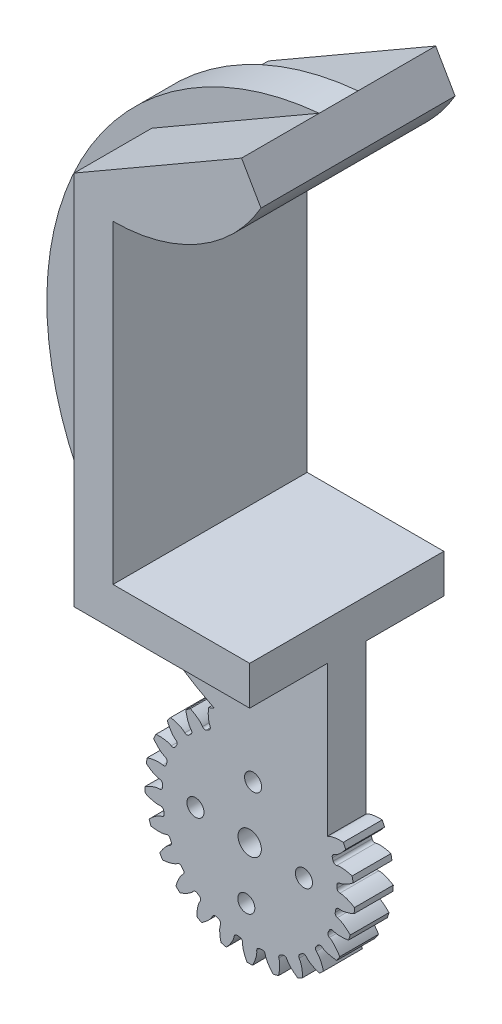
SolidWorks part; units mm, degrees
ref_plane "前视基准面" through (0, 0, 0) normal (0, 0, 1) x (1, 0, 0)
ref_plane "上视基准面" through (0, 0, 0) normal (0, 1, 0) x (1, 0, 0)
ref_plane "右视基准面" through (0, 0, 0) normal (1, 0, 0) x (0, 0, -1)
ref_axis "Axis1" through (0, 0, -88.99) along (0, 0, 1)
sketch "草图1" plane through (0, 0, 0) normal (0, 0, 1) x (1, 0, 0)
  circle A0 centre (0, 0) radius 13.5
extrude "LaShenA" add sketch "草图1" along normal blind 5
sketch "SketchA" plane through (0, 0, 5) normal (0, 0, 1) x (1, 0, 0)
  line L0 (0, 0) -> (0, 13.5) construction
  arc A0 (0.1684, 11.2487) -> (-0.1684, 11.2487) centre (0, 0) ccw
  arc A1 (1.8042, 14.0286) -> (-1.8042, 14.0286) centre (0, 0) ccw
  arc A2 (-0.1684, 11.2487) -> (-0.5533, 11.6043) centre (-0.1741, 11.6287) cw
  arc A3 (0.5533, 11.6043) -> (0.1684, 11.2487) centre (0.1741, 11.6287) cw
  circle A4 centre (0, 0) radius 11.7462 construction
  circle A5 centre (0, 0) radius 13.5 construction
  circle A6 centre (0, 0) radius 11.25 construction
  circle A7 centre (0, 0) radius 12.5 construction
  spline S0 degree 3 poles (0.5533, 11.6043) (0.5561, 11.6473) (0.5611, 11.7224) (0.5725, 11.8116) (0.5848, 11.8743) (0.5957, 11.9239) (0.6097, 11.9808) (0.6273, 12.0449) (0.6489, 12.116) (0.6746, 12.194) (0.7051, 12.2786) (0.7405, 12.3697) (0.7813, 12.4671) (0.8278, 12.5705) (0.8803, 12.6797) (0.9392, 12.7945) (1.0048, 12.9146) (1.0774, 13.0397) (1.1573, 13.1696) (1.2447, 13.3039) (1.3401, 13.4424) (1.4435, 13.5847) (1.5959, 13.7832) (1.7184, 13.9305) (1.8042, 14.0286) knots 0.117691 0.117691 0.117691 0.117691 0.158672 0.189773 0.203463 0.219643 0.238312 0.25947 0.283117 0.309254 0.337879 0.368994 0.402598 0.438691 0.477273 0.518344 0.561905 0.607955 0.656494 0.707522 0.761039 0.817046 0.875541 1 1 1 1
  spline S1 degree 3 poles (-0.5533, 11.6043) (-0.5561, 11.6473) (-0.5611, 11.7224) (-0.5725, 11.8116) (-0.5848, 11.8743) (-0.5957, 11.9239) (-0.6097, 11.9808) (-0.6273, 12.0449) (-0.6489, 12.116) (-0.6746, 12.194) (-0.7051, 12.2786) (-0.7405, 12.3697) (-0.7813, 12.4671) (-0.8278, 12.5705) (-0.8803, 12.6797) (-0.9392, 12.7945) (-1.0048, 12.9146) (-1.0774, 13.0397) (-1.1573, 13.1696) (-1.2447, 13.3039) (-1.3401, 13.4424) (-1.4435, 13.5847) (-1.5959, 13.7832) (-1.7184, 13.9305) (-1.8042, 14.0286) knots 0.117691 0.117691 0.117691 0.117691 0.158672 0.189773 0.203463 0.219643 0.238312 0.25947 0.283117 0.309254 0.337879 0.368994 0.402598 0.438691 0.477273 0.518344 0.561905 0.607955 0.656494 0.707522 0.761039 0.817046 0.875541 1 1 1 1
  dimension "D1" = 0.38
  dimension "Db" = 23.4923
  dimension "Da" = 27
  dimension "Df" = 22.5
  dimension "Dn" = 25
extrude "Cut-ExtrudeA" cut sketch "SketchA" against normal blind 30
pattern_circular "www.KYTool.cn" count 25 over 360 about axis through (0, 0, -88.99) along (0, 0, 1) of "Cut-ExtrudeA"
sketch "草图3" plane through (0, 0, 5) normal (0, 0, 1) x (1, 0, 0)
  line L0 (0, 0) -> (10, 0) construction
  line L1 (10, 0) -> (10, 30)
  line L2 (5, 8.6603) -> (5, 25)
  line L3 (10, 30) -> (-7.6, 30)
  line L4 (-7.6, 30) -> (-7.6, 70.5)
  line L5 (-7.6, 70.5) -> (11.4526, 81.5) construction
  line L6 (5, 25) -> (-12.6, 25)
  line L7 (-12.6, 25) -> (-12.6, 73.3868)
  line L8 (-12.6, 73.3868) -> (8.9526, 85.8301)
  line L9 (8.9526, 85.8301) -> (11.4526, 81.5)
  line L10 (5, 0) -> (5, 8.6603) construction
  line L11 (5, 0) -> (5, 25) construction
  line L12 (-7.6, 70.5) -> (11.9902, 70.5) construction
  arc A0 (10, 0) -> (5, 8.6603) centre (0, 0) ccw
  arc A1 (5, 8.6603) -> (10, 0) centre (0, 0) ccw construction
  arc A2 (-7.6, 70.5) -> (11.4526, 81.5) centre (-7.6, 92.5) ccw
  dimension "D1" = 20
  dimension "D3" = 30
  dimension "D4" = 17.6
  dimension "D5" = 40.5
  dimension "D6" = 22
  dimension "D7" = 120
  dimension "D2" = 5
extrude "凸台-拉伸2" add sketch "草图3" against normal blind 15 and the other way blind 10
sketch "草图4" plane through (0, 0, 15) normal (0, 0, 1) x (1, 0, 0)
  line L0 (10, 0) -> (10, 30) construction
  line L1 (5, 25) -> (5, 8.6603) construction
  line L2 (10, 0) -> (10, 25)
  line L3 (5, 25) -> (5, 8.6603)
  line L4 (5, 25) -> (10, 25)
  arc A0 (10, 0) -> (5, 8.6603) centre (0, 0) ccw construction
  arc A1 (10, 0) -> (5, 8.6603) centre (0, 0) ccw
extrude "切除-拉伸2" cut sketch "草图4" against normal blind 10 contours L2 L4 L3 A1
sketch "草图5" plane through (0, 0, 5) normal (0, 0, 1) x (1, 0, 0)
  line L0 (-4.6338, 12.6798) -> (-4.6031, 12.742)
  line L1 (12.5, -0.6289) -> (12.5, 47.3711) construction
  line L2 (8.9526, 85.8301) -> (-12.6, 73.3868) construction
  line L3 (-12.6, 73.3868) -> (-12.6, 25) construction
  line L4 (-12.6, 25) -> (10, 25) construction
  line L5 (5, 25) -> (5, 12.5399) construction
  line L6 (8.9526, 85.8301) -> (-12.6, 73.3868)
  line L7 (-12.6, 73.3868) -> (-12.6, 25)
  line L8 (-12.6, 25) -> (5, 25)
  line L9 (5, 25) -> (5, 9.4839)
  arc A0 (8.9526, 85.8301) -> (-4.6031, 12.742) centre (12.5, 47.3711) ccw
  arc A1 (5, 9.4839) -> (12.5, 8.7487) centre (12.5, 47.3711) ccw construction
  arc A2 (-2.6343, 10.9372) -> (-2.9606, 10.8535) centre (0, 0) ccw construction
  arc A3 (-2.6343, 10.9372) -> (-2.3499, 11.3773) centre (-2.7233, 11.3067) ccw construction
  arc A4 (-3.4218, 11.1021) -> (-2.9606, 10.8535) centre (-3.0606, 11.2201) ccw construction
  arc A5 (-2.6343, 10.9372) -> (-2.9606, 10.8535) centre (0, 0) ccw
  arc A6 (-2.6343, 10.9372) -> (-2.3499, 11.3773) centre (-2.7233, 11.3067) ccw
  arc A7 (-3.4218, 11.1021) -> (-2.9606, 10.8535) centre (-3.0606, 11.2201) ccw
  arc A8 (-2.3887, 11.7338) -> (5, 9.4839) centre (12.5, 47.3711) ccw
  spline S0 degree 3 poles (-1803.1915, -858.3735) (17.3324, 6.3385) (-1.7835, 6.7674) (-2.3829, 11.5829) (-2.3866, 11.6466) (-2.3884, 11.6974) (-2.3889, 11.7561) (-2.3878, 11.8225) (-2.3847, 11.8968) (-2.3791, 11.9787) (-2.3706, 12.0682) (-2.359, 12.1652) (-2.3437, 12.2697) (-2.3244, 12.3814) (-2.3007, 12.5003) (-2.2722, 12.6261) (-2.2385, 12.7587) (-2.1993, 12.898) (-2.1542, 13.0436) (4.9269, 33.9999) (120.1949, 16.7852) (-1959.1511, -398.1966) knots -4.422768 -4.422768 -4.422768 -4.422768 0.158672 0.189773 0.203463 0.219643 0.238312 0.25947 0.283117 0.309254 0.337879 0.368994 0.402598 0.438691 0.477273 0.518344 0.561905 0.607955 0.656494 0.707522 21.732971 21.732971 21.732971 21.732971 only from (-2.3499, 11.3773) to (-2.0479, 13.3438) construction
  spline S1 degree 3 poles (1908.6731, 594.8932) (-113.4147, -43.1959) (-20.6971, 27.4209) (-4.396, 12.4681) (-4.2864, 12.3621) (-4.185, 12.259) (-4.0916, 12.159) (-4.006, 12.0624) (-3.9279, 11.9697) (-3.8572, 11.8811) (-3.7935, 11.7969) (-3.7365, 11.7175) (-3.686, 11.6431) (-3.6416, 11.574) (-3.6031, 11.5105) (-3.5701, 11.4528) (-3.5423, 11.4012) (-3.5194, 11.3558) (-3.4919, 11.2982) (-1.6974, 6.7897) (-18.2411, -2.7949) (1993.4996, 116.4854) knots -20.61536 -20.61536 -20.61536 -20.61536 0.41017 0.461198 0.509737 0.555786 0.599347 0.640418 0.679001 0.715094 0.748698 0.779812 0.808438 0.834574 0.858221 0.879379 0.898048 0.914228 0.927918 0.959019 5.540328 5.540328 5.540328 5.540328 only from (-4.6338, 12.6798) to (-3.4218, 11.1021) construction
  spline S2 degree 3 poles (-2.3499, 11.3773) (-2.358, 11.4197) (-2.3718, 11.4936) (-2.3829, 11.5829) (-2.3866, 11.6466) (-2.3882, 11.6909) (-2.3886, 11.7208) (-2.3887, 11.7338) knots 0.117691 0.117691 0.117691 0.117691 0.158672 0.189773 0.203463 0.219643 0.232056 0.232056 0.232056 0.232056
  spline S3 degree 3 poles (-4.6338, 12.6798) (-4.5523, 12.6105) (-4.4346, 12.5053) (-4.2864, 12.3621) (-4.185, 12.259) (-4.0916, 12.159) (-4.006, 12.0624) (-3.9279, 11.9697) (-3.8572, 11.8811) (-3.7935, 11.7969) (-3.7365, 11.7175) (-3.686, 11.6431) (-3.6416, 11.574) (-3.6031, 11.5105) (-3.5701, 11.4528) (-3.5423, 11.4012) (-3.5194, 11.3558) (-3.4919, 11.2982) (-3.4587, 11.2146) (-3.4352, 11.1431) (-3.4218, 11.1021) knots 0.358993 0.358993 0.358993 0.358993 0.461198 0.509737 0.555786 0.599347 0.640418 0.679001 0.715094 0.748698 0.779812 0.808438 0.834574 0.858221 0.879379 0.898048 0.914228 0.927918 0.959019 1 1 1 1
  dimension "D2" = 48
extrude "凸台-拉伸3" add sketch "草图5" against normal blind 5 contours A0 L9 L8 L7 L6 region at (-13.0266, 42.4329, 5)
sketch "草图6" plane through (0, 0, -10) normal (0, 0, -1) x (-1, 0, 0)
  line L0 (-5, 25) -> (-5, 8.6603) construction
  line L1 (-10, 0) -> (-10, 30) construction
  line L2 (-5, 25) -> (-5, 8.6603)
  line L3 (-10, 0) -> (-10, 25)
  line L4 (-5, 25) -> (-10, 25)
  arc A1 (-5, 8.6603) -> (-10, 0) centre (9.2705, -5.3523) ccw
extrude "切除-拉伸3" cut sketch "草图6" against normal blind 10
sketch "草图7" plane through (0, 0, 5) normal (0, 0, 1) x (1, 0, 0)
  line L0 (-8.084, 0.5086) -> (-5.8884, 0.3705) construction
  line L1 (-13.4734, 0.8477) -> (-8.084, 0.5086) construction
  line L2 (1.497, -0.0942) -> (5.8884, -0.3705) construction
  line L3 (-5.8884, 0.3705) -> (-1.497, 0.0942) construction
  line L4 (-1.497, 0.0942) -> (1.497, -0.0942) construction
  line L5 (8.084, -0.5086) -> (13.4734, -0.8477) construction
  line L6 (5.8884, -0.3705) -> (8.084, -0.5086) construction
  arc A0 (13.446, -1.206) -> (13.4911, -0.4888) centre (0, 0) ccw construction
  circle A3 centre (0, 0) radius 1.5
  circle A6 centre (-6.9862, 0.4395) radius 1.1
  circle A7 centre (0.4395, 6.9862) radius 1.1
  circle A8 centre (6.9862, -0.4395) radius 1.1
  circle A9 centre (-0.4395, -6.9862) radius 1.1
  point P7 (0, 0)
  point P20 (0, 0)
  point P21 (0, 0)
  dimension "D1" = 2.2
  dimension "D2" = 7
  dimension "D5" = 3
  dimension "D3" = 4
extrude "切除-拉伸4" cut sketch "草图7" against normal through all
sketch "草图8" plane through (0, 0, 5) normal (0, 0, 1) x (1, 0, 0)
  line L0 (10, 8.842) -> (10, 7.1893)
  arc A0 (10.6273, 8.3253) -> (10.1692, 8.879) centre (0, 0) ccw construction
  arc A1 (10.1692, 8.879) -> (10, 8.842) centre (11.4744, 2.5136) ccw construction
  arc A2 (10.6273, 8.3253) -> (10.1692, 8.879) centre (0, 0) ccw
  arc A3 (10.1692, 8.879) -> (10, 8.842) centre (11.4744, 2.5136) ccw
  spline S0 degree 3 poles (1155.5754, -1631.4041) (-76.128, 94.515) (19.683, 28.1576) (10.4994, 8.0337) (10.4325, 7.8967) (10.3657, 7.7684) (10.2995, 7.6486) (10.2341, 7.5374) (10.1701, 7.4345) (10.1076, 7.3399) (3.0897, -2.732) (-50.1959, 20.3748) (-1229.1453, 1576.6035) knots -20.61528 -20.61528 -20.61528 -20.61528 0.41017 0.461198 0.509737 0.555786 0.599347 0.640418 0.679001 0.715094 0.748698 12.40242 12.40242 12.40242 12.40242 only from (10.6273, 8.3253) to (10, 7.1893) construction
  spline S1 degree 3 poles (10.6273, 8.3253) (10.5865, 8.2264) (10.5229, 8.0819) (10.4325, 7.8967) (10.3657, 7.7684) (10.2995, 7.6486) (10.2341, 7.5374) (10.1701, 7.4345) (10.1076, 7.3399) (10.0513, 7.2589) (10.0154, 7.2099) (10, 7.1893) knots 0.358993 0.358993 0.358993 0.358993 0.461198 0.509737 0.555786 0.599347 0.640418 0.679001 0.715094 0.748698 0.773183 0.773183 0.773183 0.773183
extrude "切除-拉伸5" cut sketch "草图8" against normal blind 10
